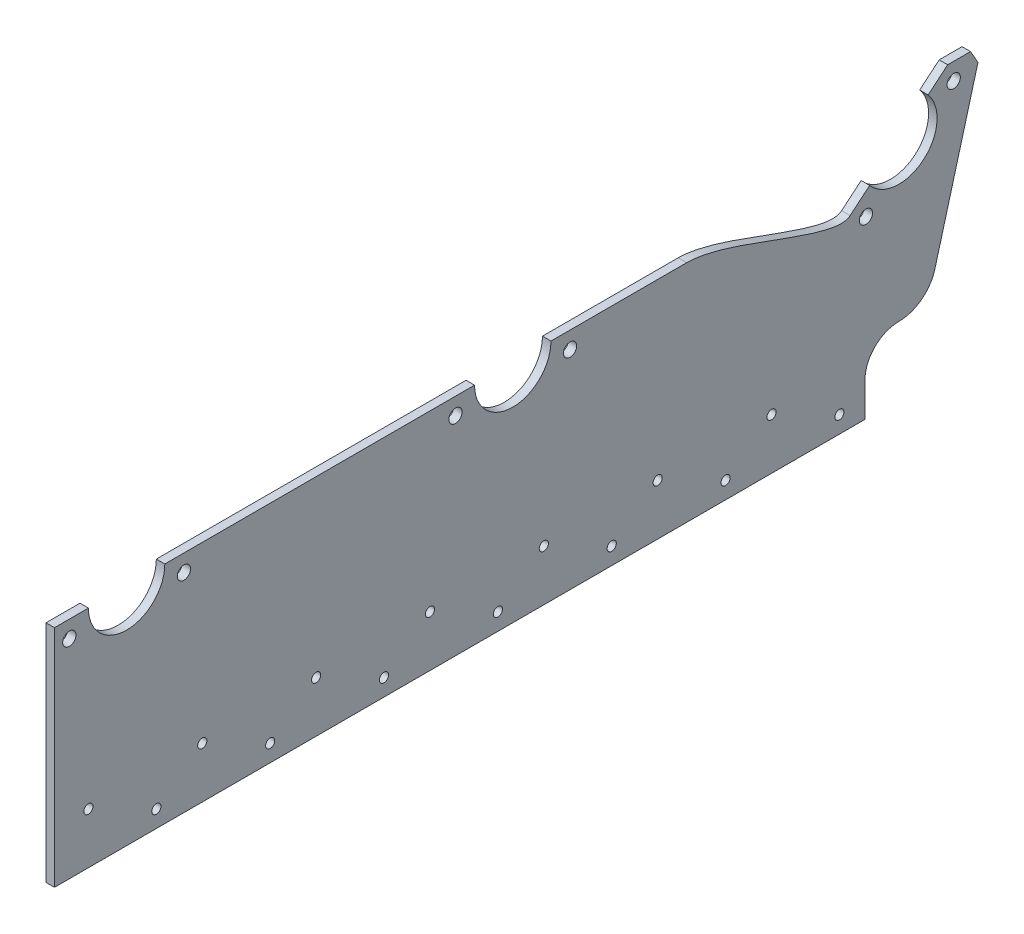
SolidWorks part; units mm, degrees
material "6061 Alloy"
ref_plane "Front Plane" through (0, 0, 0) normal (0, 0, 1) x (1, 0, 0)
ref_plane "Top Plane" through (0, 0, 0) normal (0, 1, 0) x (1, 0, 0)
ref_plane "Right Plane" through (0, 0, 0) normal (1, 0, 0) x (0, 0, -1)
sketch "Sketch1" plane through (0, 0, 0) normal (1, 0, 0) x (0, 0, -1)
  line L0 (-12.7, -12.7) -> (-315.9125, -12.7)
  line L1 (-315.9125, -12.7) -> (-315.9125, 71.4375)
  line L2 (-315.9125, 71.4375) -> (-303.2125, 71.4375)
  line L3 (-274.6375, 71.4375) -> (-158.75, 71.4375)
  line L5 (10.9449, 80.6213) -> (18.2432, 86.7453)
  line L7 (-315.9125, 12.7) -> (13.4735, 12.7) construction
  line L8 (-12.7, -12.7) -> (-12.7, 0)
  line L9 (0, 12.4079) -> (0, 12.7) construction
  line L10 (13.4735, 22.9788) -> (30.9432, 86.7453)
  line L12 (-10.9449, 62.2537) -> (10.9449, 80.6213) construction
  line L13 (18.2432, 86.7453) -> (30.9432, 86.7453)
  line L14 (-130.175, 71.4375) -> (-79.375, 71.4375)
  line L15 (-10.9449, 62.2537) -> (-18.2432, 56.1297)
  line L16 (-315.9125, 15.875) -> (13.4735, 15.875) construction
  line L17 (-288.925, 71.4375) -> (-144.4625, 71.4375) construction
  line L18 (0, 71.4375) -> (-144.4625, 71.4375) construction
  arc A3 (0, 12.7) -> (13.4735, 22.9788) centre (0, 26.67) ccw
  arc A4 (0, 12.7) -> (-12.7, 0) centre (0, 0) ccw
  circle A5 centre (0, 0) radius 12.4079 construction
  arc A6 (-303.2125, 71.4375) -> (-274.6375, 71.4375) centre (-288.925, 71.4375) ccw
  arc A7 (-158.75, 71.4375) -> (-130.175, 71.4375) centre (-144.4625, 71.4375) ccw
  arc A8 (-10.9449, 62.2537) -> (10.9449, 80.6213) centre (0, 71.4375) ccw
  spline S0 degree 3 poles (-18.2432, 56.1297) (-24.729, 50.6874) (-62.4417, 71.4375) (-79.375, 71.4375) knots 0 0 0 0 1 1 1 1
  point P4 (-164.3062, -12.7)
  dimension "D1" = 25.4
  dimension "D3" = 12.7
  dimension "D5" = 28.575
  dimension "D6" = 41.275
  dimension "D7" = 13.97
  dimension "D8" = 12.7
  dimension "D10" = 24.8158
  dimension "D13" = 9.5273
  dimension "D14" = 140
  dimension "D15" = 50.8
  dimension "D16" = 50.8
  dimension "D17" = 25.4
  dimension "D2" = 0
  dimension "D4" = 12.7
  dimension "D9" = 12.7
  dimension "D11" = 288.925
  dimension "D12" = 288.925
  dimension "D18" = 3.175
extrude "Boss-Extrude1" add sketch "Sketch1" along normal blind 3.175
hole_wizard "#10 Clearance Hole1" positions "Sketch2" profile "Sketch3" hole size "#10" standard "ANSI Inch" end condition through all
sketch "Sketch2" plane through (3.175, 0, 0) normal (1, 0, 0) x (0, 0, -1)
  line L0 (-310.3562, 65.0875) -> (-267.4937, 65.0875) construction
  line L2 (-165.8938, 65.0875) -> (-123.0312, 65.0875) construction
  line L4 (-12.3356, 52.7974) -> (20.499, 80.3489) construction
  line L6 (-303.2125, 71.4375) -> (-315.9125, 71.4375) construction
  line L7 (-288.925, 65.0875) -> (-288.925, 71.4375) construction
  line L9 (-144.4625, 71.4375) -> (-144.4625, 65.0875) construction
  line L11 (0, 71.4375) -> (4.0817, 66.5731) construction
  line L14 (18.2432, 86.7453) -> (10.9449, 80.6213) construction
  line L15 (18.2432, 86.7453) -> (10.9449, 80.6213) construction
  point P0 (-310.3562, 65.0875)
  point P2 (-267.4937, 65.0875)
  point P4 (-165.8938, 65.0875)
  point P6 (-123.0312, 65.0875)
  point P8 (-12.3356, 52.7974)
  point P10 (20.499, 80.3489)
  dimension "D1" = 42.8625
  dimension "D2" = 6.35
  dimension "D3" = 6.35
sketch "Sketch3" plane through (3.175, 65.0875, 310.3562) normal (0, 1, 0) x (0, 0, -1)
  line L0 (0, 0) -> (0, 3.175)
  line L1 (0, 3.175) -> (2.4892, 3.175)
  line L2 (2.4892, 3.175) -> (2.4892, 0)
  line L5 (2.4892, 0) -> (0, 0)
  line L11 (0, -6.35) -> (0, 107.95) construction
  dimension "Thru Hole Dia." = 4.9784
  dimension "Thru Hole Depth" = 3.175
chamfer "Chamfer1" distance 5.08 angle 45 1 edges at (1.5875, 86.7453, -30.9432) first distance on face at (1.5875, 54.862, -22.2083)
hole_wizard "1/8 (0.135) Diameter Hole1" positions "Sketch4" profile "Sketch5" hole size "1/8" standard "ANSI Inch"
sketch "Sketch4" plane through (3.175, 0, 0) normal (1, 0, 0) x (0, 0, -1)
  line L0 (-315.9125, -12.7) -> (-12.7, -12.7) construction
  line L1 (-12.7, -12.7) -> (-12.7, 0) construction
  line L2 (-315.9125, 71.4375) -> (-315.9125, -12.7) construction
  point P0 (-22.2504, -6.35)
  point P2 (-47.6504, 6.35)
  point P14 (-64.8441, -6.35)
  point P15 (-90.2441, 6.35)
  point P16 (-107.4378, -6.35)
  point P17 (-132.8378, 6.35)
  point P18 (-150.0314, -6.35)
  point P19 (-175.4315, 6.35)
  point P20 (-192.6251, -6.35)
  point P21 (-218.0251, 6.35)
  point P22 (-235.2188, -6.35)
  point P23 (-260.6188, 6.35)
  point P24 (-277.8125, -6.35)
  point P25 (-303.2125, 6.35)
  dimension "D1" = 6.35
  dimension "D2" = 9.5504
  dimension "D3" = 12.7
  dimension "D4" = 25.4
  dimension "D6" = 12.7
  dimension "D5" = 7
sketch "Sketch5" plane through (3.175, -6.35, 22.2504) normal (0, 1, 0) x (0, 0, -1)
  line L0 (0, 0) -> (0, 17.5402)
  line L1 (0, 17.5402) -> (1.7145, 16.51)
  line L2 (1.7145, 16.51) -> (1.7145, 0)
  line L5 (1.7145, 0) -> (0, 0)
  line L10 (0, 17.5402) -> (-1.7145, 16.51) construction
  line L11 (0, -6.35) -> (0, 107.95) construction
  dimension "Hole Dia." = 3.429
  dimension "Hole Depth" = 16.51
  dimension "Drill Angle" = 118
